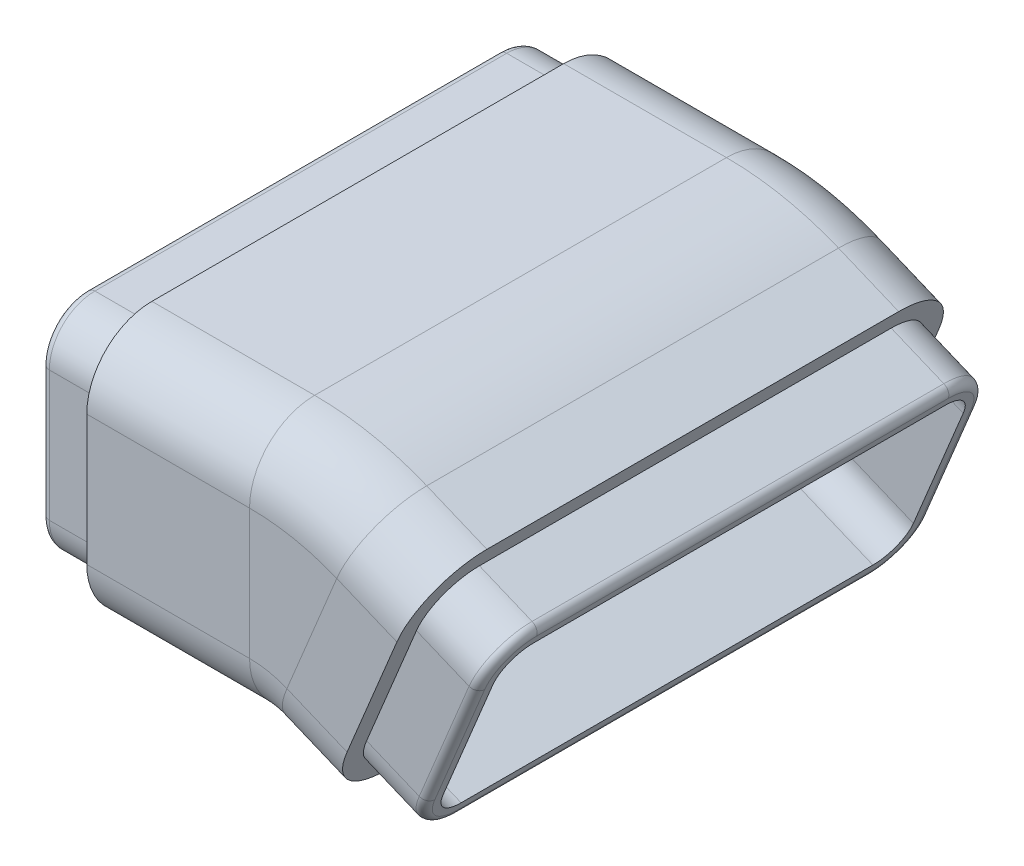
SolidWorks part; units mm, degrees
ref_plane "Front" through (0, 0, 0) normal (0, 0, 1) x (1, 0, 0)
ref_plane "Top" through (0, 0, 0) normal (0, 1, 0) x (1, 0, 0)
ref_plane "Right" through (0, 0, 0) normal (1, 0, 0) x (0, 0, -1)
sketch "Sketch2path" plane through (0, 0, 0) normal (0, 0, 1) x (1, 0, 0)
  line L0 (13.8268, -0.7612) -> (17.5224, -2.2919)
  line L1 (0, 0) -> (10, 0)
  arc A1 (10, 0) -> (13.8268, -0.7612) centre (10, -10) cw
  point P5 (11.9891, 0)
  dimension "D1" = 10
  dimension "D2" = 22.5
  dimension "D4" = 10
  dimension "D3" = 4
sketch "Sketch3" plane through (0, 0, 0) normal (1, 0, 0) x (0, 0, -1)
  line L0 (-16.65, -4) -> (-16.65, 4)
  line L1 (-12.65, 8) -> (12.65, 8)
  line L2 (16.65, 4) -> (16.65, -4)
  line L3 (12.65, -8) -> (-12.65, -8)
  line L4 (-15.65, -4) -> (-15.65, 4)
  line L5 (12.65, -7) -> (-12.65, -7)
  line L6 (0, 91.8161) -> (0, -91.8161) construction
  line L12 (15.65, 4) -> (15.65, -4)
  line L13 (-12.65, 7) -> (12.65, 7)
  arc A0 (-12.65, 8) -> (-16.65, 4) centre (-12.65, 4) ccw
  arc A1 (16.65, 4) -> (12.65, 8) centre (12.65, 4) ccw
  arc A2 (12.65, -8) -> (16.65, -4) centre (12.65, -4) ccw
  arc A3 (-16.65, -4) -> (-12.65, -8) centre (-12.65, -4) ccw
  arc A4 (-12.65, 7) -> (-15.65, 4) centre (-12.65, 4) ccw
  arc A5 (12.65, 7) -> (15.65, 4) centre (12.65, 4) cw
  arc A6 (15.65, -4) -> (12.65, -7) centre (12.65, -4) cw
  arc A7 (-15.65, -4) -> (-12.65, -7) centre (-12.65, -4) ccw
  point P31 (0, 0)
  dimension "D1" = 4
sweep "Sweep1" add profiles "Sketch3" path "Sketch2path"
ref_point "Point1S1"
ref_point "Point2S3"
ref_axis "os podluzna S1" through (0, 0, 0) along (-1, 0, 0)
ref_axis "os podluzna S3" through (17.5224, -2.2919, 0) along (0.9239, -0.3827, 0)
ref_plane "Plane4 polowki" through (0, 0, 0) normal (0, 0, 1) x (1, 0, 0)
sketch "Sketch4" plane through (0, 0, 0) normal (-1, 0, 0) x (0, 0, 1)
  line L0 (15.65, 4) -> (15.65, -4) construction
  line L1 (-12.65, 7) -> (12.65, 7) construction
  line L2 (-15.65, -4) -> (-15.65, 4) construction
  line L3 (12.65, -7) -> (-12.65, -7) construction
  line L4 (15.65, 4) -> (15.65, -4)
  line L5 (-12.65, 7) -> (12.65, 7)
  line L6 (-15.65, -4) -> (-15.65, 4)
  line L7 (12.65, -7) -> (-12.65, -7)
  line L8 (14.45, 4) -> (14.45, -4)
  line L9 (12.65, -5.8) -> (-12.65, -5.8)
  line L10 (-14.45, -4) -> (-14.45, 4)
  line L11 (-12.65, 5.8) -> (12.65, 5.8)
  arc A4 (15.65, 4) -> (12.65, 7) centre (12.65, 4) ccw
  arc A5 (-12.65, 7) -> (-15.65, 4) centre (-12.65, 4) ccw
  arc A6 (-15.65, -4) -> (-12.65, -7) centre (-12.65, -4) ccw
  arc A7 (12.65, -7) -> (15.65, -4) centre (12.65, -4) ccw
  arc A8 (12.65, -5.8) -> (14.45, -4) centre (12.65, -4) ccw
  arc A9 (-14.45, -4) -> (-12.65, -5.8) centre (-12.65, -4) ccw
  arc A10 (-12.65, 5.8) -> (-14.45, 4) centre (-12.65, 4) ccw
  arc A11 (14.45, 4) -> (12.65, 5.8) centre (12.65, 4) ccw
  dimension "D1" = 1.2
extrude "Boss-Extrude1" add sketch "Sketch4" along normal mid plane 8
sketch "Sketch5" plane through (-4, 0, 0) normal (-1, 0, 0) x (0, 0, 1)
  line L10 (12.65, 6.8) -> (-12.65, 6.8)
  line L11 (-15.45, 4) -> (-15.45, -4)
  line L12 (-12.65, -6.8) -> (12.65, -6.8)
  line L13 (15.45, -4) -> (15.45, 4)
  line L14 (12.65, 6.8) -> (-12.65, 6.8)
  line L15 (-15.45, 4) -> (-15.45, -4)
  line L16 (-12.65, -6.8) -> (12.65, -6.8)
  line L17 (15.45, -4) -> (15.45, 4)
  arc A8 (15.45, 4) -> (12.65, 6.8) centre (12.65, 4) ccw
  arc A9 (-12.65, 6.8) -> (-15.45, 4) centre (-12.65, 4) ccw
  arc A10 (-15.45, -4) -> (-12.65, -6.8) centre (-12.65, -4) ccw
  arc A11 (12.65, -6.8) -> (15.45, -4) centre (12.65, -4) ccw
  arc A12 (15.45, 4) -> (12.65, 6.8) centre (12.65, 4) ccw
  arc A13 (-12.65, 6.8) -> (-15.45, 4) centre (-12.65, 4) ccw
  arc A14 (-15.45, -4) -> (-12.65, -6.8) centre (-12.65, -4) ccw
  arc A15 (12.65, -6.8) -> (15.45, -4) centre (12.65, -4) ccw
  dimension "D1" = 0.2
extrude "Cut-Extrude1" cut sketch "Sketch5" against normal up to surface (4 mm away) flip side to cut up to face at (0, 0, 0)
fillet "Fillet1" radius 0.5 24 edges at (4, 0, -15.65) (4, 7, 0) (4, 0, 15.65) (4, -5.2728, -13.9228) (4, 0, -14.45) (4, 5.2728, -13.9228) (4, 5.8, 0) (4, 5.2728, 13.9228) (4, 0, 14.45) (4, -5.2728, 13.9228) (-4, -5.9799, -14.6299) (-4, 0, -15.45) (-4, 5.9799, -14.6299) (-4, 6.8, 0) (-4, 5.9799, 14.6299) (-4, 0, 15.45) (-4, -5.9799, 14.6299) (4, -7, 0) (4, -5.8, 0) (-4, -6.8, 0) (4, -6.1213, -14.7713) (4, 6.1213, -14.7713) (4, 6.1213, 14.7713) (4, -6.1213, 14.7713)
sketch "Sketch6" plane through (15.7666, -6.5307, 0) normal (0.9239, -0.3827, 0) x (0, 0, -1)
  line L0 (-15.65, 8.588) -> (-15.65, 0.588) construction
  line L1 (12.65, 11.588) -> (-12.65, 11.588) construction
  line L2 (15.65, 0.588) -> (15.65, 8.588) construction
  line L3 (-12.65, -2.412) -> (12.65, -2.412) construction
  line L4 (-15.65, 8.588) -> (-15.65, 0.588)
  line L5 (12.65, 11.588) -> (-12.65, 11.588)
  line L6 (15.65, 0.588) -> (15.65, 8.588)
  line L7 (-12.65, -2.412) -> (12.65, -2.412)
  line L8 (-14.45, 8.588) -> (-14.45, 0.588)
  line L9 (-12.65, -1.212) -> (12.65, -1.212)
  line L10 (14.45, 0.588) -> (14.45, 8.588)
  line L11 (12.65, 10.388) -> (-12.65, 10.388)
  arc A4 (-15.65, 0.588) -> (-12.65, -2.412) centre (-12.65, 0.588) ccw
  arc A5 (-12.65, 11.588) -> (-15.65, 8.588) centre (-12.65, 8.588) ccw
  arc A6 (15.65, 8.588) -> (12.65, 11.588) centre (12.65, 8.588) ccw
  arc A7 (12.65, -2.412) -> (15.65, 0.588) centre (12.65, 0.588) ccw
  arc A8 (-14.45, 0.588) -> (-12.65, -1.212) centre (-12.65, 0.588) ccw
  arc A9 (12.65, -1.212) -> (14.45, 0.588) centre (12.65, 0.588) ccw
  arc A10 (14.45, 8.588) -> (12.65, 10.388) centre (12.65, 8.588) ccw
  arc A11 (-12.65, 10.388) -> (-14.45, 8.588) centre (-12.65, 8.588) ccw
  dimension "D1" = 1.2
extrude "Boss-Extrude2" add sketch "Sketch6" along normal mid plane 8
sketch "Sketch9" plane through (19.4621, -8.0615, 0) normal (0.9239, -0.3827, 0) x (0, 0, -1)
  line L8 (-12.65, -2.212) -> (12.65, -2.212)
  line L9 (15.45, 0.588) -> (15.45, 8.588)
  line L10 (12.65, 11.388) -> (-12.65, 11.388)
  line L11 (-15.45, 8.588) -> (-15.45, 0.588)
  line L12 (-12.65, -2.212) -> (12.65, -2.212)
  line L13 (15.45, 0.588) -> (15.45, 8.588)
  line L14 (12.65, 11.388) -> (-12.65, 11.388)
  line L15 (-15.45, 8.588) -> (-15.45, 0.588)
  arc A8 (-15.45, 0.588) -> (-12.65, -2.212) centre (-12.65, 0.588) ccw
  arc A9 (12.65, -2.212) -> (15.45, 0.588) centre (12.65, 0.588) ccw
  arc A10 (15.45, 8.588) -> (12.65, 11.388) centre (12.65, 8.588) ccw
  arc A11 (-12.65, 11.388) -> (-15.45, 8.588) centre (-12.65, 8.588) ccw
  arc A12 (-15.45, 0.588) -> (-12.65, -2.212) centre (-12.65, 0.588) ccw
  arc A13 (12.65, -2.212) -> (15.45, 0.588) centre (12.65, 0.588) ccw
  arc A14 (15.45, 8.588) -> (12.65, 11.388) centre (12.65, 8.588) ccw
  arc A15 (-12.65, 11.388) -> (-15.45, 8.588) centre (-12.65, 8.588) ccw
  dimension "D1" = 0.2
extrude "Cut-Extrude2" cut sketch "Sketch9" against normal up to surface (4 mm away) flip side to cut up to face at (17.5224, -2.2919, 0)
fillet "Fillet2" radius 0.5 16 edges at (13.8268, -0.7612, 14.45) (15.8446, 4.1102, 13.9228) (16.0464, 4.5973, 0) (15.8446, 4.1102, -13.9228) (13.8268, -0.7612, -14.45) (11.809, -5.6326, -13.9228) (11.6073, -6.1197, 0) (18.9295, -9.3474, 14.6299) (21.2179, -3.8227, 15.45) (23.5063, 1.702, 14.6299) (23.8201, 2.4597, 0) (23.5063, 1.702, -14.6299) (21.2179, -3.8227, -15.45) (18.9295, -9.3474, -14.6299) (11.809, -5.6326, 13.9228) (18.6156, -10.1051, 0)
